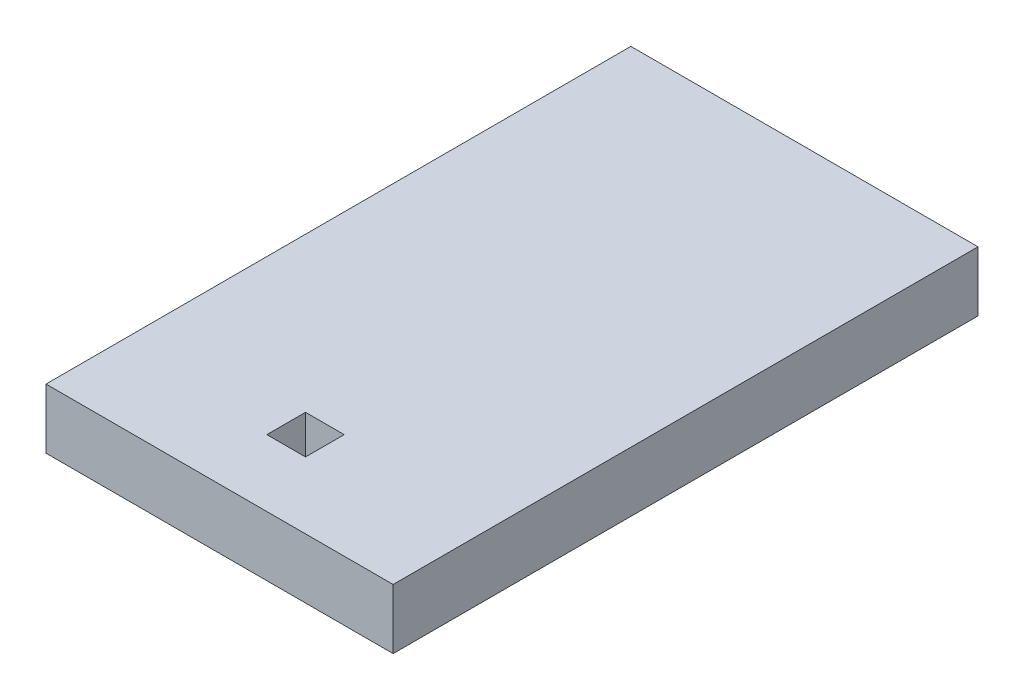
SolidWorks part; units mm, degrees
ref_plane "Front Plane" through (0, 0, 0) normal (0, 0, 1) x (1, 0, 0)
ref_plane "Top Plane" through (0, 0, 0) normal (0, 1, 0) x (1, 0, 0)
ref_plane "Right Plane" through (0, 0, 0) normal (1, 0, 0) x (0, 0, -1)
sketch "Sketch1" plane through (0, 0, 0) normal (0, 1, 0) x (1, 0, 0)
  line L0 (0, 15.5) -> (0, 0) construction
  line L1 (-9.2, 15.5) -> (9.2, 15.5)
  line L2 (-9.2, 15.5) -> (-9.2, -15.5)
  line L3 (-9.2, -15.5) -> (9.2, -15.5)
  line L4 (9.2, 15.5) -> (9.2, -15.5)
  line L5 (0, -9.9192) -> (0, 0) construction
  line L6 (-1.025, -9.9192) -> (1.025, -9.9192)
  line L7 (-1.025, -9.9192) -> (-1.025, -11.9692)
  line L8 (-1.025, -11.9692) -> (1.025, -11.9692)
  line L9 (1.025, -9.9192) -> (1.025, -11.9692)
  line L11 (-9.2, 15.5) -> (-12.375, 15.5)
  line L12 (-9.2, 15.5) -> (-9.2, -15.5)
  line L13 (-9.2, -15.5) -> (-12.375, -15.5)
  line L14 (-12.375, 15.5) -> (-12.375, -15.5)
  point P14 (9.2, 0)
  dimension "D1" = 18.4
  dimension "D2" = 31
  dimension "D3" = 3.5308
  dimension "D4" = 2.05
  dimension "D5" = 3.175
extrude "Boss-Extrude1" add sketch "Sketch1" along normal blind 3.175 contours L4 L1 L2 L3 L6 L9 L8 L7 | L11 L14 L13 L2 region at (0, 0, -0.0812) region at (-10.7875, 0, 0)
sketch "Sketch2" plane through (0, 3.175, 0) normal (0, 1, 0) x (1, 0, 0)
  line L0 (-12.375, -15.5) -> (9.2, -15.5) construction
  line L1 (-12.375, 15.5) -> (-9.2, 15.5)
  line L2 (-12.375, 15.5) -> (-12.375, -15.5)
  line L3 (-12.375, -15.5) -> (-9.2, -15.5)
  line L4 (-9.2, 15.5) -> (-9.2, -15.5)
  dimension "D1" = 3.175
extrude "Cut-Extrude1" cut sketch "Sketch2" against normal through all
equation "\"bottomThickness\"= .220in"
equation "\"wallThickness\"= .125in"
equation "\"D1@Sketch2\"=\"wallThickness\""
equation "\"D1@Boss-Extrude1\"=\"wallThickness\""
